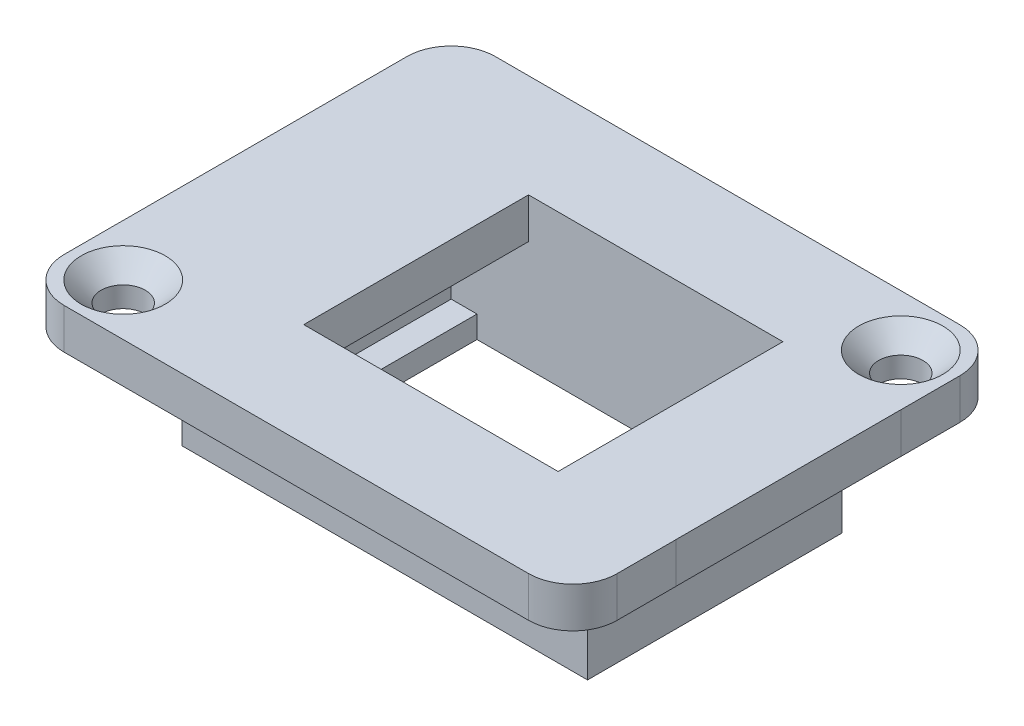
SolidWorks part; units mm, degrees
ref_plane "Front Plane" through (0, 0, 0) normal (0, 0, 1) x (1, 0, 0)
ref_plane "Top Plane" through (0, 0, 0) normal (0, 1, 0) x (1, 0, 0)
ref_plane "Right Plane" through (0, 0, 0) normal (1, 0, 0) x (0, 0, -1)
sketch "Sketch1" plane through (0, 0, 0) normal (0, 0, 1) x (1, 0, 0)
  line L0 (-5.75, 0) -> (10.25, 0) construction
  line L1 (10.25, 0) -> (10.25, -6.5) construction
  line L2 (10.25, -8) -> (11.75, -8) construction
  line L3 (-10.25, -10) -> (-10.25, -13.8781) construction
  line L4 (11.75, -8) -> (10.25, -6.5) construction
  line L5 (10.25, -8) -> (10.25, -9.5)
  line L6 (10.25, -10) -> (-5.75, -10) construction
  line L7 (-8.75, -8) -> (-8.75, -13.8781) construction
  line L8 (-5.75, 0) -> (-5.75, -10) construction
  line L9 (-5.75, 0) -> (-5.75, -8) construction
  line L10 (10.25, 0) -> (10.25, -8) construction
  line L11 (-10.25, -5) -> (-8.75, -8) construction
  line L12 (-10.25, -5) -> (-11.25, -8) construction
  line L13 (-11.75, -8) -> (-10, -8)
  line L14 (-8.75, -5) -> (-8.75, -10) construction
  line L15 (-10.25, -5) -> (-10.25, -10) construction
  line L16 (-8.75, -13.8781) -> (-10.25, -13.8781) construction
  line L19 (10.7534, 0.75) -> (10.7534, -1.9966)
  line L22 (10.25, -8) -> (11.75, -8)
  line L23 (11.75, -8) -> (11.75, -1.9966)
  line L27 (13.75, -1.9966) -> (18.75, -1.9966)
  line L33 (2.25, 0) -> (2.25, -10) construction
  line L47 (-11.75, -8) -> (-11.75, -1.9966)
  line L51 (-13.75, -1.9966) -> (-13.75, -9.5)
  line L53 (-13.75, -1.9966) -> (-18.75, -1.9966)
  line L59 (13.75, -1.9966) -> (13.75, -9.5)
  line L60 (18.75, 0.75) -> (18.75, -1.9966)
  line L61 (-18.75, 0.75) -> (-18.75, -1.9966)
  line L64 (-6.5034, -1.9966) -> (-11.75, -1.9966)
  line L65 (10.7534, -1.9966) -> (11.75, -1.9966)
  line L69 (-10, -9.5) -> (-10, -8)
  line L70 (-13.75, -9.5) -> (-10, -9.5)
  line L71 (-11.75, -9.5) -> (-10, -9.5) construction
  line L72 (10.25, -9.5) -> (13.75, -9.5)
  line L73 (10.25, -9.5) -> (11.75, -9.5) construction
  line L74 (-6.5034, 0.75) -> (-6.5034, -1.9966)
  line L75 (-6.5034, 0.75) -> (-18.75, 0.75)
  line L76 (10.7534, 0.75) -> (18.75, 0.75)
  dimension "D1" = 27.5
  dimension "D2" = 5
  dimension "D3" = 1.5
  dimension "D4" = 16
  dimension "D5" = 1.5
  dimension "D6" = 6.5
  dimension "D7" = 10
  dimension "D8" = 5
  dimension "D9" = 20.25
extrude "Boss-Extrude1" add sketch "Sketch1" along normal blind 15.25
sketch "Sketch2" plane through (0, 0, 15.25) normal (0, 0, 1) x (1, 0, 0)
  line L2 (18.7534, -1.9966) -> (-18.7534, -1.9966)
  line L4 (-18.7534, -1.9966) -> (-18.7534, 0.75)
  line L5 (18.7534, 0.75) -> (18.7534, -1.9966)
  line L7 (-18.7534, 0.75) -> (18.7534, 0.75)
extrude "Boss-Extrude2" add sketch "Sketch2" along normal blind 7
sketch "Sketch3" plane through (0, 0, 0) normal (0, 0, -1) x (-1, 0, 0)
  line L2 (18.7534, -1.9966) -> (-18.7534, -1.9966)
  line L4 (-18.7534, -1.9966) -> (-18.7534, 0.75)
  line L5 (18.7534, 0.75) -> (18.7534, -1.9966)
  line L7 (-18.7534, 0.75) -> (18.7534, 0.75)
extrude "Boss-Extrude3" add sketch "Sketch3" along normal blind 7
sketch "Sketch9" plane through (0, -1.9966, 0) normal (0, -1, 0) x (1, 0, 0)
  line L0 (18.75, 15.25) -> (18.75, 0) construction
  line L1 (18.7534, -7) -> (-18.7534, -7) construction
  line L2 (-18.75, 15.25) -> (-18.75, 0) construction
  line L3 (-18.7534, 22.25) -> (18.7534, 22.25) construction
  circle A1 centre (-15.25, 18.75) radius 1.5
  circle A5 centre (15.25, -3.5) radius 1.5
  dimension "D1" = 3.5
  dimension "D3" = 3.5
  dimension "D2" = 3.5
  dimension "D4" = 3.5
extrude "Cut-Extrude1" cut sketch "Sketch9" against normal blind 12
fillet "Fillet1" radius 3 4 edges at (18.7534, -0.6233, 22.25) (-18.7534, -0.6233, 22.25) (-18.7534, -0.6233, -7) (18.7534, -0.6233, -7)
sketch "Sketch10" plane through (0, 0.75, 0) normal (0, 1, 0) x (1, 0, 0)
  circle A0 centre (-15.25, -18.75) radius 2.85
  circle A1 centre (15.25, 3.5) radius 2.85
extrude "Cut-Extrude2" cut sketch "Sketch10" against normal blind 6 draft 45
sketch "Sketch11" plane through (0, -1.9966, 0) normal (0, -1, 0) x (1, 0, 0)
  line L0 (-13.75, 15.25) -> (13.75, 15.25)
  line L21 (-13.75, 16.25) -> (13.75, 16.25)
  line L22 (-11.75, 16.25) -> (-6.2534, 16.25) construction
  line L25 (-11.75, 15.25) -> (-6.2534, 15.25) construction
  line L26 (-13.75, 15.25) -> (-13.75, 16.25)
  line L27 (13.75, 15.25) -> (13.75, 16.25)
  line L28 (13.75, 0) -> (13.75, -1)
  line L29 (-13.75, 0) -> (-13.75, -1)
  line L30 (-13.75, -1) -> (13.75, -1)
  line L31 (-13.75, 0) -> (13.75, 0)
extrude "Boss-Extrude5" add sketch "Sketch11" along normal up to vertex (7.5034 mm away) contours L21 L27 L0 L26 | L28 L30 L29 L31 up to point (-13.75, -9.5, 15.25)
